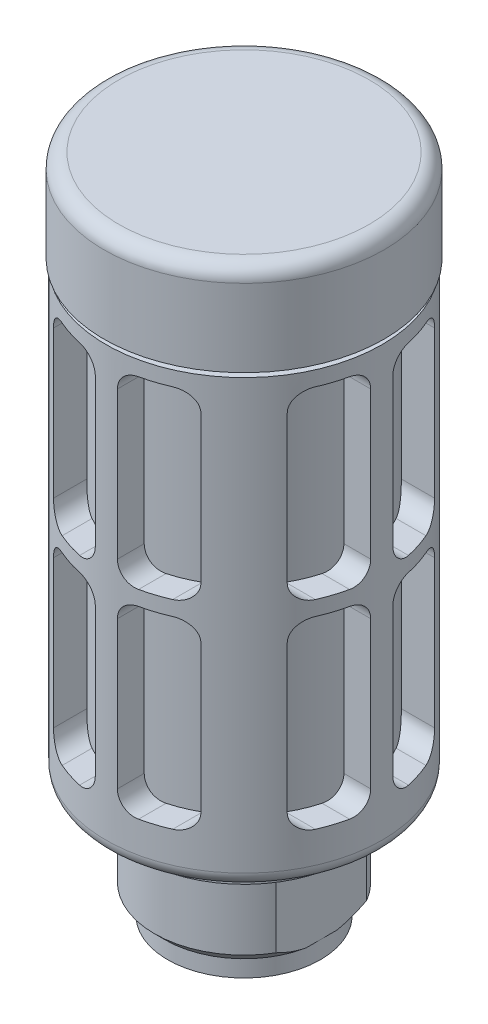
SolidWorks part; units mm, degrees
ref_plane "Ebene vorne" through (0, 0, 0) normal (0, 0, 1) x (1, 0, 0)
ref_plane "Ebene oben" through (0, 0, 0) normal (0, 1, 0) x (1, 0, 0)
ref_plane "Ebene rechts" through (0, 0, 0) normal (1, 0, 0) x (0, 0, -1)
sketch "Skizze1" plane through (0, 0, 0) normal (0, 0, 1) x (1, 0, 0)
  line L0 (0, 34.9) -> (-6.05, 34.9)
  line L1 (-6.05, 34.9) -> (-6.05, 7.8)
  line L2 (-6.05, 7.8) -> (-3.2, 7.8)
  line L3 (-3.2, 7.8) -> (-3.2, 0.4)
  line L4 (-3.2, 0.4) -> (-3.6, 0)
  line L5 (-3.6, 0) -> (-4.15, 0)
  line L6 (-4.15, 0) -> (-4.15, 1)
  line L7 (-4.15, 1) -> (-4.283, 1)
  line L8 (-4.283, 1) -> (-4.864, 1.581)
  line L9 (-4.864, 1.581) -> (-4.864, 5.5)
  line L10 (-4.864, 5.5) -> (-5.7, 5.5)
  line L11 (-5.7, 5.5) -> (-5.7, 6.1)
  line L12 (-6.1, 6.5) -> (-6.7, 6.5)
  line L13 (-7.5, 7.3) -> (-7.5, 30.6)
  line L14 (-7.5, 30.6) -> (-7, 30.6)
  line L15 (-6.8, 30.8) -> (-6.8, 30.9)
  line L16 (-6.8, 30.9) -> (-7.6, 30.9)
  line L17 (-7.6, 30.9) -> (-7.6, 35.1)
  line L18 (-6.8, 35.9) -> (0, 35.9)
  line L19 (0, 35.9) -> (0, 34.9)
  line L20 (0, 35.9) -> (0, 0) construction
  arc A0 (-5.7, 6.1) -> (-6.1, 6.5) centre (-6.1, 6.1) ccw
  arc A1 (-6.7, 6.5) -> (-7.5, 7.3) centre (-6.7, 7.3) cw
  arc A2 (-7, 30.6) -> (-6.8, 30.8) centre (-7, 30.8) ccw
  arc A3 (-7.6, 35.1) -> (-6.8, 35.9) centre (-6.8, 35.1) cw
revolve "Rotation1" add sketch "Skizze1" angle 360 about L20 reverse direction yes
cosmetic thread "Gewindedarstellung1" parameters "D1"=3.5, "D2"=8.566
sketch "Skizze2" plane through (0, 0, 0) normal (0, 0, 1) x (1, 0, 0)
  line L0 (1.6, 19.8) -> (3, 19.8)
  line L1 (4, 20.8) -> (4, 28.8)
  line L2 (3, 29.8) -> (1.6, 29.8)
  line L3 (0.6, 28.8) -> (0.6, 20.8)
  arc A0 (0.6, 20.8) -> (1.6, 19.8) centre (1.6, 20.8) ccw
  arc A1 (3, 19.8) -> (4, 20.8) centre (3, 20.8) ccw
  arc A2 (4, 28.8) -> (3, 29.8) centre (3, 28.8) ccw
  arc A3 (1.6, 29.8) -> (0.6, 28.8) centre (1.6, 28.8) ccw
extrude "Schnitt-Linear austragen1" cut sketch "Skizze2" along normal blind 20 and the other way blind 20
sketch "Skizze3" plane through (0, 0, 0) normal (0, 0, 1) x (1, 0, 0)
  line L0 (1.6, 9) -> (3, 9)
  line L1 (4, 10) -> (4, 18)
  line L2 (3, 19) -> (1.6, 19)
  line L3 (0.6, 18) -> (0.6, 10)
  arc A0 (0.6, 10) -> (1.6, 9) centre (1.6, 10) ccw
  arc A1 (3, 9) -> (4, 10) centre (3, 10) ccw
  arc A2 (4, 18) -> (3, 19) centre (3, 18) ccw
  arc A3 (1.6, 19) -> (0.6, 18) centre (1.6, 18) ccw
extrude "Schnitt-Linear austragen2" cut sketch "Skizze3" along normal blind 20 and the other way blind 20
sketch "Skizze4" plane through (0, 0, 0) normal (0, 0, 1) x (1, 0, 0)
  line L0 (-3, 19.8) -> (-1.6, 19.8)
  line L1 (-0.6, 20.8) -> (-0.6, 28.8)
  line L2 (-1.6, 29.8) -> (-3, 29.8)
  line L3 (-4, 28.8) -> (-4, 20.8)
  arc A0 (-4, 20.8) -> (-3, 19.8) centre (-3, 20.8) ccw
  arc A1 (-1.6, 19.8) -> (-0.6, 20.8) centre (-1.6, 20.8) ccw
  arc A2 (-0.6, 28.8) -> (-1.6, 29.8) centre (-1.6, 28.8) ccw
  arc A3 (-3, 29.8) -> (-4, 28.8) centre (-3, 28.8) ccw
extrude "Schnitt-Linear austragen3" cut sketch "Skizze4" along normal blind 20 and the other way blind 20
sketch "Skizze5" plane through (0, 0, 0) normal (0, 0, 1) x (1, 0, 0)
  line L0 (-3, 9) -> (-1.6, 9)
  line L1 (-0.6, 10) -> (-0.6, 18)
  line L2 (-1.6, 19) -> (-3, 19)
  line L3 (-4, 18) -> (-4, 10)
  arc A0 (-4, 10) -> (-3, 9) centre (-3, 10) ccw
  arc A1 (-1.6, 9) -> (-0.6, 10) centre (-1.6, 10) ccw
  arc A2 (-0.6, 18) -> (-1.6, 19) centre (-1.6, 18) ccw
  arc A3 (-3, 19) -> (-4, 18) centre (-3, 18) ccw
extrude "Schnitt-Linear austragen4" cut sketch "Skizze5" along normal blind 20 and the other way blind 20
sketch "Skizze6" plane through (0, 0, 0) normal (1, 0, 0) x (0, 0, -1)
  line L0 (-3, 19.8) -> (-1.6, 19.8)
  line L1 (-0.6, 20.8) -> (-0.6, 28.8)
  line L2 (-1.6, 29.8) -> (-3, 29.8)
  line L3 (-4, 28.8) -> (-4, 20.8)
  arc A0 (-4, 20.8) -> (-3, 19.8) centre (-3, 20.8) ccw
  arc A1 (-1.6, 19.8) -> (-0.6, 20.8) centre (-1.6, 20.8) ccw
  arc A2 (-0.6, 28.8) -> (-1.6, 29.8) centre (-1.6, 28.8) ccw
  arc A3 (-3, 29.8) -> (-4, 28.8) centre (-3, 28.8) ccw
extrude "Schnitt-Linear austragen5" cut sketch "Skizze6" along normal blind 20 and the other way blind 20
sketch "Skizze7" plane through (0, 0, 0) normal (1, 0, 0) x (0, 0, -1)
  line L0 (-3, 9) -> (-1.6, 9)
  line L1 (-0.6, 10) -> (-0.6, 18)
  line L2 (-1.6, 19) -> (-3, 19)
  line L3 (-4, 18) -> (-4, 10)
  arc A0 (-4, 10) -> (-3, 9) centre (-3, 10) ccw
  arc A1 (-1.6, 9) -> (-0.6, 10) centre (-1.6, 10) ccw
  arc A2 (-0.6, 18) -> (-1.6, 19) centre (-1.6, 18) ccw
  arc A3 (-3, 19) -> (-4, 18) centre (-3, 18) ccw
extrude "Schnitt-Linear austragen6" cut sketch "Skizze7" along normal blind 20 and the other way blind 20
sketch "Skizze8" plane through (0, 0, 0) normal (1, 0, 0) x (0, 0, -1)
  line L0 (1.6, 19.8) -> (3, 19.8)
  line L1 (4, 20.8) -> (4, 28.8)
  line L2 (3, 29.8) -> (1.6, 29.8)
  line L3 (0.6, 28.8) -> (0.6, 20.8)
  arc A0 (0.6, 20.8) -> (1.6, 19.8) centre (1.6, 20.8) ccw
  arc A1 (3, 19.8) -> (4, 20.8) centre (3, 20.8) ccw
  arc A2 (4, 28.8) -> (3, 29.8) centre (3, 28.8) ccw
  arc A3 (1.6, 29.8) -> (0.6, 28.8) centre (1.6, 28.8) ccw
extrude "Schnitt-Linear austragen7" cut sketch "Skizze8" along normal blind 20 and the other way blind 20
sketch "Skizze9" plane through (0, 0, 0) normal (1, 0, 0) x (0, 0, -1)
  line L0 (1.6, 9) -> (3, 9)
  line L1 (4, 10) -> (4, 18)
  line L2 (3, 19) -> (1.6, 19)
  line L3 (0.6, 18) -> (0.6, 10)
  arc A0 (0.6, 10) -> (1.6, 9) centre (1.6, 10) ccw
  arc A1 (3, 9) -> (4, 10) centre (3, 10) ccw
  arc A2 (4, 18) -> (3, 19) centre (3, 18) ccw
  arc A3 (1.6, 19) -> (0.6, 18) centre (1.6, 18) ccw
extrude "Schnitt-Linear austragen8" cut sketch "Skizze9" along normal blind 20 and the other way blind 20
sketch "Skizze10" plane through (0, 0, 0) normal (0, 0, 1) x (1, 0, 0)
  line L0 (-6.2, -11.5) -> (6.2, -11.5)
  line L1 (6.2, -11.5) -> (6.2, 5.5)
  line L2 (6.2, 5.5) -> (4.2, 5.5)
  line L3 (4.2, 5.5) -> (4.2, -9.5)
  line L4 (4.2, -9.5) -> (-4.2, -9.5)
  line L5 (-4.2, -9.5) -> (-4.2, 5.5)
  line L6 (-4.2, 5.5) -> (-6.2, 5.5)
  line L7 (-6.2, 5.5) -> (-6.2, -11.5)
extrude "Schnitt-Linear austragen9" cut sketch "Skizze10" along normal blind 15 and the other way blind 15
sketch "Skizze11" plane through (0, 0, 0) normal (0, 0, 1) x (1, 0, 0)
  line L0 (0, 32.2) -> (-2.2, 32.2)
  line L1 (-3.2, 31.2) -> (-3.2, 7.8)
  line L2 (-3.2, 7.8) -> (-6.05, 7.8)
  line L3 (-6.05, 7.8) -> (-6.05, 34.9)
  line L4 (-6.05, 34.9) -> (0, 34.9)
  line L5 (0, 34.9) -> (0, 32.2)
  line L6 (0, 34.9) -> (0, 7.8) construction
  arc A0 (-2.2, 32.2) -> (-3.2, 31.2) centre (-2.2, 31.2) ccw
revolve "Rotation2" add sketch "Skizze11" angle 360 about L6 reverse direction yes
ref_plane "Ebene1" through (0, 5.5, 0) normal (0, 1, 0) x (1, 0, 0)
ref_plane "ANBAU XY" through (0, 5.5, 0) normal (0, 1, 0) x (1, 0, 0)
ref_plane "ANBAU XZ" through (0, 0, 0) normal (0, 0, 1) x (1, 0, 0)
ref_plane "ANBAU YZ" through (0, 0, 0) normal (1, 0, 0) x (0, 0, -1)
ref_axis "ANBAU X" through (-80.9, 5.5, 0) along (1, 0, 0)
ref_axis "ANBAU Y" through (0, 5.5, 50) along (0, 0, -1)
ref_axis "ANBAU Z" through (0, 50, 0) along (0, -1, 0)
sketch3d "ANBAU"
  point P0 (0, 5.5, 0)
ref_plane "ANBAU_STD XY" through (0, 5.5, 0) normal (0, 1, 0) x (1, 0, 0)
ref_plane "ANBAU_STD XZ" through (0, 0, 0) normal (0, 0, 1) x (1, 0, 0)
ref_plane "ANBAU_STD YZ" through (0, 0, 0) normal (1, 0, 0) x (0, 0, -1)
ref_axis "ANBAU_STD X" through (-80.9, 5.5, 0) along (1, 0, 0)
ref_axis "ANBAU_STD Y" through (0, 5.5, 50) along (0, 0, -1)
ref_axis "ANBAU_STD Z" through (0, 50, 0) along (0, -1, 0)
sketch3d "ANBAU_STD"
  point P0 (0, 5.5, 0)
